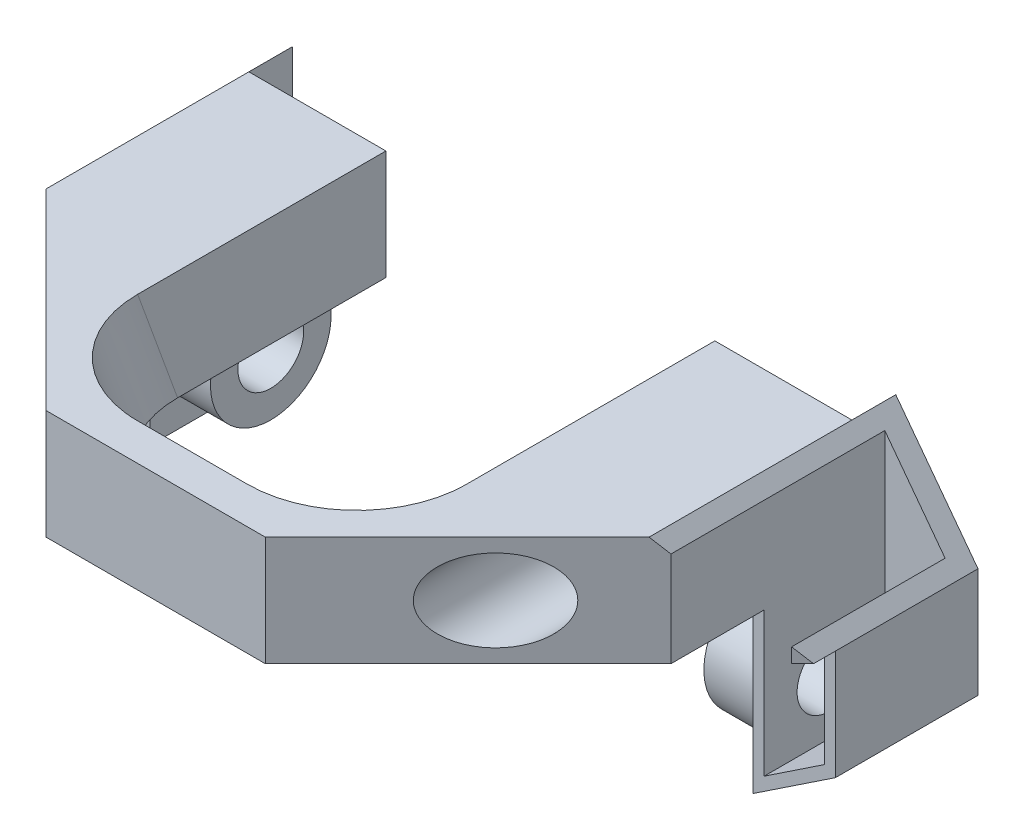
SolidWorks part; units mm, degrees
ref_plane "Front Plane" through (0, 0, 0) normal (0, 0, 1) x (1, 0, 0)
ref_plane "Top Plane" through (0, 0, 0) normal (0, 1, 0) x (1, 0, 0)
ref_plane "Right Plane" through (0, 0, 0) normal (1, 0, 0) x (0, 0, -1)
sketch "Sketch1" plane through (0, 0, 0) normal (0, 0, 1) x (1, 0, 0)
  line L0 (-27.5, 0) -> (27.5, 0)
  line L1 (27.5, 0) -> (27.5, -15)
  line L2 (27.5, -15) -> (35, -10)
  line L3 (35, -10) -> (35, 0)
  line L4 (35, 0) -> (27.5, 10)
  line L5 (27.5, 10) -> (-27.5, 10)
  line L6 (-27.5, 10) -> (-35, 0)
  line L7 (-35, 0) -> (-35, -10)
  line L8 (-35, -10) -> (-27.5, -15)
  line L9 (-27.5, -15) -> (-27.5, 0)
  line L10 (-27.5, 10) -> (-27.5, 0) construction
  line L11 (27.5, 10) -> (27.5, 0) construction
  line L12 (35, 0) -> (27.5, 0) construction
  line L13 (-27.5, 0) -> (-35, 0) construction
  line L14 (-27.5, -15) -> (27.5, -15) construction
  line L15 (-35, -10) -> (35, -10) construction
  point P11 (-35, 0)
  dimension "D1" = 70
  dimension "D2" = 55
  dimension "D3" = 15
  dimension "D4" = 10
  dimension "D5" = 10
extrude "Boss-Extrude1" add sketch "Sketch1" along normal blind 40
chamfer "Chamfer1" distance 25 angle 45 2 edges at (35, -5, 40) (-35, -5, 40)
sketch "Sketch3" plane through (0, 0, 0) normal (0, 0, -1) x (-1, 0, 0)
  line L1 (-27.5, -15.4249) -> (27.5, -15.4249)
  line L2 (-27.5, -15.4249) -> (-27.5, 15.4249)
  line L3 (-27.5, 15.4249) -> (27.5, 15.4249)
  line L4 (27.5, -15.4249) -> (27.5, 15.4249)
  line L5 (-27.5, -15.4249) -> (27.5, 15.4249) construction
  line L6 (-27.5, 15.4249) -> (27.5, -15.4249) construction
  point P0 (0, 0)
  dimension "D1" = 55
extrude "Cut-Extrude2" cut sketch "Sketch3" against normal blind 4
sketch "Sketch5" plane through (0, 0, 0) normal (0, 0, -1) x (-1, 0, 0)
  line L0 (-20.5, 5) -> (20.5, 5) construction
  line L1 (0, 5) -> (0, 0) construction
  circle A0 centre (-20.5, 5) radius 1.75
  circle A1 centre (20.5, 5) radius 1.75
  dimension "D1" = 3.5
  dimension "D2" = 41
  dimension "D3" = 5
extrude "Cut-Extrude4" cut sketch "Sketch5" against normal through all
sketch "Sketch4" plane through (0, 0, 40) normal (0, 0, 1) x (1, 0, 0)
  line L3 (-35, 0) -> (-27.5, 10) construction
  line L4 (-34, 1.3333) -> (-28.5, 8.6667)
  line L6 (-34, -9.4648) -> (-34, 0)
  line L7 (-28.5, -13.1315) -> (-34, -9.4648)
  line L8 (-28.5, 0) -> (-28.5, -13.1315)
  line L9 (-34, -9.4648) -> (-34, 1.3333)
  line L10 (-28.5, -13.1315) -> (-34, -9.4648)
  line L11 (-28.5, 8.6667) -> (-28.5, -13.1315)
  dimension "D1" = 1
extrude "Cut-Extrude3" cut sketch "Sketch4" against normal blind 38
sketch "Sketch6" plane through (-27.5, 0, 0) normal (1, 0, 0) x (0, 0, -1)
  line L0 (0, -15) -> (0, 10) construction
  line L1 (-22.5, -15) -> (0, -15) construction
  circle A0 centre (-7, -8) radius 3
  circle A1 centre (-7, -8) radius 5.5
  dimension "D3" = 6
  dimension "D1" = 7
  dimension "D2" = 7
  dimension "D4" = 2.5
extrude "Boss-Extrude2" add sketch "Sketch6" along normal blind 5
sketch "Sketch7" plane through (-27.5, 0, 0) normal (1, 0, 0) x (0, 0, -1)
  circle A1 centre (-7, -8) radius 3
  circle A2 centre (-7, -8) radius 3
  dimension "D1" = 0
extrude "Cut-Extrude5" cut sketch "Sketch7" against normal blind 2
mirror "Mirror1" about plane through (0, 0, 0) normal (1, 0, 0) of "Cut-Extrude5", "Boss-Extrude2", "Cut-Extrude3"
sketch "Sketch8" plane through (0, 0, 0) normal (1, 0, 0) x (0, 0, -1)
  line L0 (-22.5, -3.3302) -> (-22.5, -15)
  line L1 (-22.5, -15) -> (-22.5, 0) construction
  line L2 (-22.5, -15) -> (-9.8835, -15)
  line L3 (-22.5, -15) -> (0, -15) construction
  line L4 (-9.8835, -15) -> (-22.5, -3.3302)
  point P8 (-17.5, -3.3302)
sketch "Sketch9" plane through (0, 0, 40) normal (0, 0, 1) x (1, 0, 0)
  circle A10 centre (-20.5, 5) radius 3.75
  circle A11 centre (-20.5, 5) radius 3.75
  circle A13 centre (20.5, 5) radius 3.75
  circle A14 centre (20.5, 5) radius 3.75
  dimension "D1" = 2
  dimension "D2" = 2
extrude "Cut-Extrude7" cut sketch "Sketch9" against normal blind 24
sketch "Sketch10" plane through (0, 0, 40) normal (0, 0, 1) x (1, 0, 0)
  line L1 (-38.1959, 0) -> (41.8615, 0)
  line L2 (-38.1959, 0) -> (-38.1959, -23.2108)
  line L3 (-38.1959, -23.2108) -> (41.8615, -23.2108)
  line L4 (41.8615, 0) -> (41.8615, -23.2108)
extrude "Cut-Extrude8" cut sketch "Sketch10" against normal blind 27
sketch "Sketch2" plane through (0, 0, 0) normal (0, -1, 0) x (1, 0, 0)
  line L0 (-27.5, 0) -> (27.5, 0) construction
  line L1 (-15, -33) -> (15, -33)
  line L2 (-15, -33) -> (-15, 23)
  line L3 (-5, 33) -> (5, 33)
  line L4 (15, -33) -> (15, 23)
  line L5 (-15, -33) -> (15, 33) construction
  line L6 (-15, 33) -> (15, -33) construction
  arc A0 (5, 33) -> (15, 23) centre (5, 23) cw
  arc A1 (-15, 23) -> (-5, 33) centre (-5, 23) cw
  point P0 (0, 0)
  dimension "D3" = 10
  dimension "D1" = 30
  dimension "D2" = 33
sketch "Sketch11" plane through (0, 0, 0) normal (1, 0, 0) x (0, 0, -1)
  line L0 (0, 0) -> (-9.227, 25.3509)
  line L1 (0, 0) -> (0, 10) construction
  dimension "D1" = 20
sweep "Cut-Sweep1" cut profiles "Sketch2" path "Sketch11"
